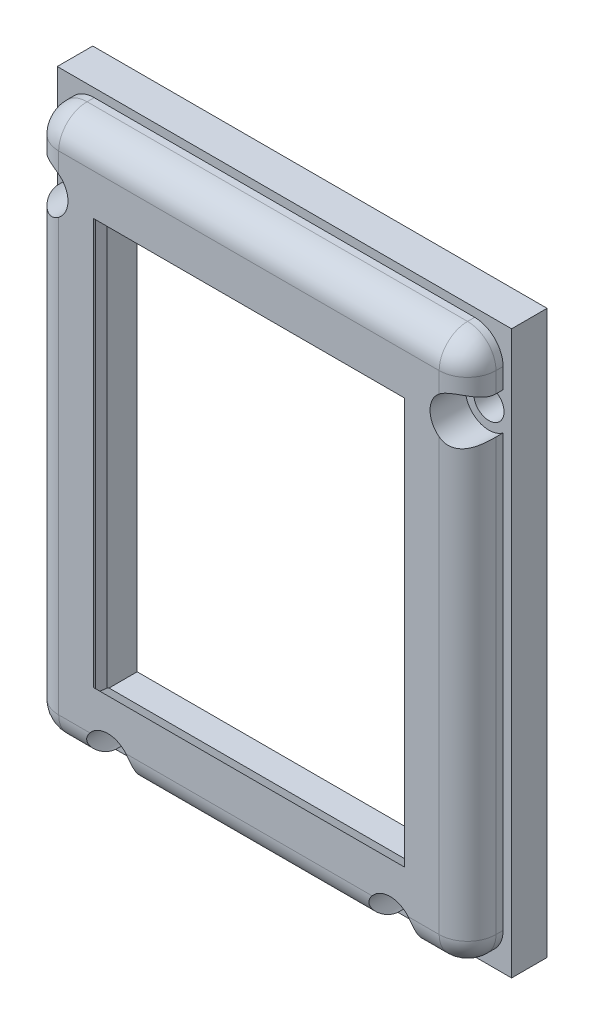
SolidWorks part; units mm, degrees
ref_plane "Front Plane" through (0, 0, 0) normal (0, 0, 1) x (1, 0, 0)
ref_plane "Top Plane" through (0, 0, 0) normal (0, 1, 0) x (1, 0, 0)
ref_plane "Right Plane" through (0, 0, 0) normal (1, 0, 0) x (0, 0, -1)
sketch "Model" plane through (0, 0, 0) normal (0, 0, 1) x (1, 0, 0)
  line L0 (0, 0) -> (114.2864, 0) construction
  line L1 (114.2864, 0) -> (114.2864, 50.7864) construction
  line L2 (114.2864, 50.7864) -> (0, 50.7864) construction
  line L3 (0, 50.7864) -> (0, 0) construction
  line L4 (13.1379, 4.5435) -> (23.2721, 4.5435) construction
  line L5 (23.2721, 4.5435) -> (23.2721, 42.2805) construction
  line L6 (23.2721, 42.2805) -> (13.1379, 42.2805) construction
  line L7 (13.1379, 42.2805) -> (13.1379, 4.5435) construction
  line L8 (31.4005, 4.5225) -> (41.5347, 4.5225) construction
  line L9 (41.5347, 4.5225) -> (41.5347, 42.3015) construction
  line L10 (41.5347, 42.3015) -> (31.4005, 42.3015) construction
  line L11 (31.4005, 42.3015) -> (31.4005, 4.5225) construction
  line L12 (46.2086, 7.3498) -> (78.8994, 7.3498)
  line L13 (78.8994, 7.3498) -> (78.8994, 50.0406)
  line L14 (78.8994, 50.0406) -> (46.2086, 50.0406)
  line L15 (46.2086, 50.0406) -> (46.2086, 7.3498)
  line L16 (3.8168, 33.0268) -> (8.8696, 33.0268) construction
  line L17 (8.8696, 33.0268) -> (8.8696, 43.1596) construction
  line L18 (8.8696, 43.1596) -> (3.8168, 43.1596) construction
  line L19 (3.8168, 43.1596) -> (3.8168, 33.0268) construction
  line L20 (2.5466, 21.3426) -> (10.1398, 21.3426) construction
  line L21 (10.1398, 21.3426) -> (10.1398, 29.4438) construction
  line L22 (10.1398, 29.4438) -> (2.5466, 29.4438) construction
  line L23 (2.5466, 29.4438) -> (2.5466, 21.3426) construction
  line L24 (2.5466, 8.6426) -> (10.1398, 8.6426) construction
  line L25 (10.1398, 8.6426) -> (10.1398, 16.7438) construction
  line L26 (10.1398, 16.7438) -> (2.5466, 16.7438) construction
  line L27 (2.5466, 16.7438) -> (2.5466, 8.6426) construction
  line L28 (62.554, 50.0406) -> (62.554, 7.3498) construction
  line L29 (46.2086, 28.6952) -> (78.8994, 28.6952) construction
  line L31 (42.234, 3.5492) -> (82.874, 3.5492)
  line L32 (90.991, 1.5367) -> (106.9676, 1.5367) construction
  line L33 (106.9676, 1.5367) -> (106.9676, 4.6101) construction
  line L34 (106.9676, 4.6101) -> (90.991, 4.6101) construction
  line L35 (90.991, 4.6101) -> (90.991, 1.5367) construction
  line L36 (42.234, 3.5492) -> (42.234, 53.8412)
  line L37 (42.234, 53.8412) -> (82.874, 53.8412)
  line L38 (82.874, 3.5492) -> (82.874, 53.8412)
  line L39 (42.234, 3.5492) -> (82.874, 53.8412) construction
  line L40 (42.234, 53.8412) -> (82.874, 3.5492) construction
  circle A0 centre (111.125, 47.625) radius 1.5 construction
  circle A1 centre (3.175, 47.625) radius 1.5 construction
  circle A2 centre (3.175, 3.175) radius 1.5 construction
  circle A3 centre (111.125, 3.175) radius 1.5 construction
  circle A4 centre (44.2722, 47.0662) radius 1.35
  circle A5 centre (49.9364, 5.5118) radius 1.35
  circle A6 centre (75.184, 5.5118) radius 1.35
  circle A7 centre (80.8482, 47.0662) radius 1.35
  circle A8 centre (97.79, 25.4) radius 9.3853 construction
  circle A9 centre (97.8662, 33.9598) radius 2.7686 construction
  circle A10 centre (16.764, 47.879) radius 2.7813 construction
  circle A11 centre (26.162, 47.879) radius 2.7813 construction
  circle A12 centre (35.56, 47.879) radius 2.7813 construction
  point P60 (62.554, 28.6952)
  point P63 (62.554, 28.6952)
  point P68 (0, 0)
extrude "Boss-Extrude1" add sketch "Model" along normal blind 3.175 contours L14 L15 L12 L13 | L37 L38 L31 L36 | A4 | A5 | A6 | A7 region at (62.554, 28.6952, 0)
sketch "Sketch1" plane through (0, 0, 3.175) normal (0, 0, 1) x (1, 0, 0)
  line L0 (62.554, 53.8412) -> (62.554, 3.5492) construction
  line L1 (42.234, 53.8412) -> (82.874, 53.8412) construction
  line L2 (42.234, 3.5492) -> (82.874, 3.5492) construction
  line L3 (42.234, 28.6952) -> (82.874, 28.6952) construction
  line L4 (42.234, 3.5492) -> (42.234, 53.8412) construction
  line L5 (82.874, 3.5492) -> (82.874, 53.8412) construction
  line L7 (46.2086, 7.3498) -> (78.8994, 7.3498)
  line L8 (46.2086, 7.3498) -> (46.2086, 50.0406)
  line L9 (46.2086, 50.0406) -> (78.8994, 50.0406)
  line L10 (78.8994, 7.3498) -> (78.8994, 50.0406)
  line L11 (46.2086, 7.3498) -> (78.8994, 50.0406) construction
  line L12 (46.2086, 50.0406) -> (78.8994, 7.3498) construction
  line L13 (48.6399, 10.5248) -> (76.4681, 10.5248)
  line L14 (48.6399, 10.5248) -> (48.6399, 46.8656)
  line L15 (48.6399, 46.8656) -> (76.4681, 46.8656)
  line L16 (76.4681, 10.5248) -> (76.4681, 46.8656)
  line L17 (48.6399, 10.5248) -> (76.4681, 46.8656) construction
  line L18 (48.6399, 46.8656) -> (76.4681, 10.5248) construction
  point P12 (62.554, 28.6952)
  point P13 (62.554, 28.6952)
  point P19 (62.554, 28.6952)
  dimension "D1" = 3.175
extrude "Boss-Extrude2" add sketch "Sketch1" along normal blind 3.175 separate body
sketch "Sketch2" plane through (0, 0, 3.175) normal (0, 0, 1) x (1, 0, 0)
  line L0 (62.554, 3.5492) -> (62.554, 53.8412) construction
  line L1 (42.234, 3.5492) -> (82.874, 3.5492) construction
  line L2 (42.234, 53.8412) -> (82.874, 53.8412) construction
  line L3 (82.874, 28.6952) -> (42.234, 28.6952) construction
  line L4 (82.874, 3.5492) -> (82.874, 53.8412) construction
  line L5 (42.234, 3.5492) -> (42.234, 53.8412) construction
  line L7 (82.112, 4.3112) -> (42.996, 4.3112)
  line L8 (82.112, 4.3112) -> (82.112, 53.0792)
  line L9 (82.112, 53.0792) -> (42.996, 53.0792)
  line L10 (42.996, 4.3112) -> (42.996, 53.0792)
  line L11 (82.112, 4.3112) -> (42.996, 53.0792) construction
  line L12 (82.112, 53.0792) -> (42.996, 4.3112) construction
  line L13 (78.8994, 7.3498) -> (46.2086, 7.3498)
  line L14 (78.8994, 7.3498) -> (78.8994, 50.0406)
  line L15 (78.8994, 50.0406) -> (46.2086, 50.0406)
  line L16 (46.2086, 7.3498) -> (46.2086, 50.0406)
  line L17 (78.8994, 7.3498) -> (46.2086, 50.0406) construction
  line L18 (78.8994, 50.0406) -> (46.2086, 7.3498) construction
  line L19 (78.8994, 50.0406) -> (46.2086, 50.0406) construction
  line L20 (46.2086, 50.0406) -> (46.2086, 7.3498) construction
  point P12 (62.554, 28.6952)
  point P13 (62.554, 28.6952)
  point P18 (62.554, 28.6952)
  dimension "D1" = 0.762
  dimension "D2" = 0.762
extrude "Boss-Extrude4" add sketch "Sketch2" along normal blind 3.175
fillet "Fillet1" radius 2.54 2 edges at (62.554, 4.3112, 6.35) (62.554, 53.0792, 6.35)
fillet "Fillet2" radius 2.54 10 edges at (42.996, 53.0792, 3.4925) (42.996, 52.3352, 5.6061) (42.996, 4.3112, 3.4925) (42.996, 5.0551, 5.6061) (82.112, 4.3112, 3.4925) (82.112, 5.0551, 5.6061) (82.112, 53.0792, 3.4925) (82.112, 52.3352, 5.6061) (42.996, 28.6952, 6.35) (82.112, 28.6952, 6.35)
chamfer "Chamfer9" distance 3.175 angle 42 2 edges at (48.6399, 28.6952, 3.175) (76.4681, 28.6952, 3.175) first distance on face at (48.6399, 28.6952, 4.7625) first distance on face at (76.4681, 28.6952, 4.7625)
chamfer "Chamfer10" distance 3.175 angle 45 2 edges at (62.554, 46.8656, 3.175) (62.554, 10.5248, 3.175)
sketch "Sketch4" plane through (0, 0, 0) normal (0, 0, -1) x (-1, 0, 0)
  circle A0 centre (-80.8482, 47.0662) radius 1.35
  circle A1 centre (-44.2722, 47.0662) radius 1.35
  circle A2 centre (-49.9364, 5.5118) radius 1.35
  circle A3 centre (-75.184, 5.5118) radius 1.35
  circle A4 centre (-75.184, 5.5118) radius 1.35 construction
  circle A5 centre (-49.9364, 5.5118) radius 1.35 construction
  circle A6 centre (-80.8482, 47.0662) radius 1.35 construction
  circle A8 centre (-44.2722, 47.0662) radius 1.35 construction
extrude "Cut-Extrude1" cut sketch "Sketch4" against normal through all
chamfer "Chamfer11" distance 0.889 angle 19 2 edges at (62.554, 50.0406, 3.175) (62.554, 7.3498, 3.175) first distance on face at (62.554, 48.824, 4.3916) first distance on face at (62.554, 8.5664, 4.3916)
chamfer "Chamfer12" distance 1.143 angle 19 2 edges at (46.2086, 28.6952, 3.6498) (78.8994, 28.6952, 3.6498) first distance on face at (47.0652, 28.6952, 4.6011) first distance on face at (78.0428, 28.6952, 4.6011)
sketch "Sketch5" plane through (0, 0, 6.35) normal (0, 0, 1) x (1, 0, 0)
  circle A0 centre (44.2722, 47.0662) radius 2.0955
  circle A1 centre (80.8482, 47.0662) radius 2.0955
  circle A2 centre (75.184, 5.5118) radius 2.0955
  circle A3 centre (49.9364, 5.5118) radius 2.0955
  dimension "D1" = 4.191
extrude "Cut-Extrude2" cut sketch "Sketch5" against normal up to surface (3.175 mm away) contours A0 | A1 | A2 | A3 up to face at (62.554, 28.6952, 3.175)
